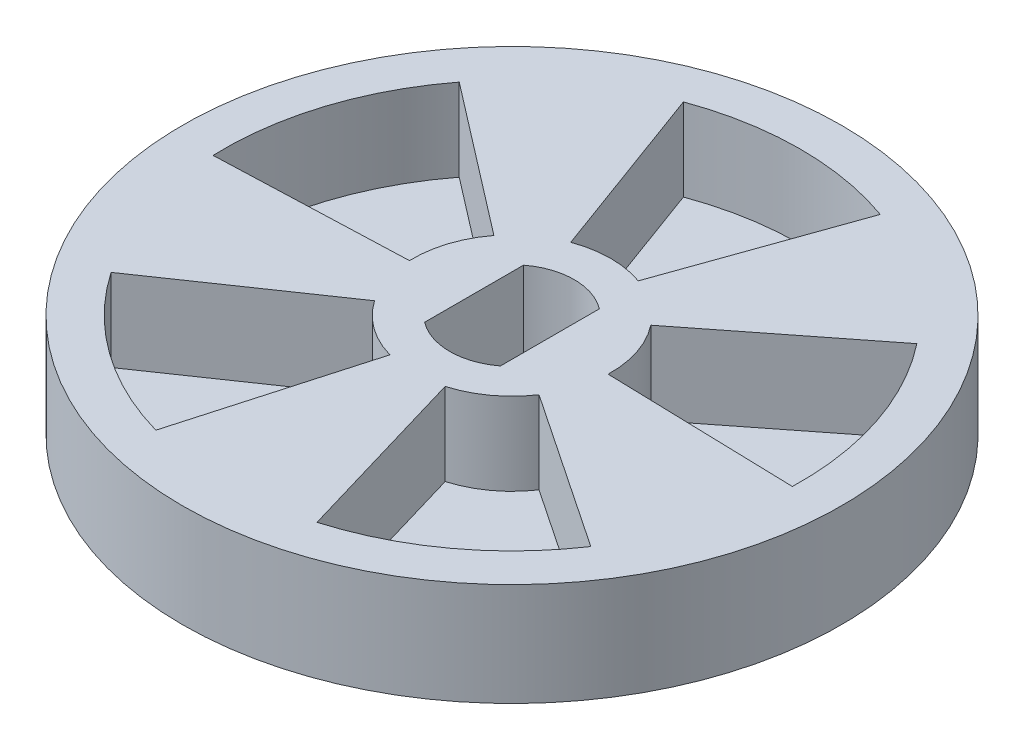
SolidWorks part; units mm, degrees
ref_plane "Front Plane" through (0, 0, 0) normal (0, 0, 1) x (1, 0, 0)
ref_plane "Top Plane" through (0, 0, 0) normal (0, 1, 0) x (1, 0, 0)
ref_plane "Right Plane" through (0, 0, 0) normal (1, 0, 0) x (0, 0, -1)
sketch "Sketch1" plane through (0, 0, 0) normal (0, 1, 0) x (1, 0, 0)
  line L0 (-2.9196, 3.81) -> (-2.9196, -3.81)
  line L1 (2.9196, 3.81) -> (2.9196, -3.81)
  circle A0 centre (0, 0) radius 4.8
  circle A1 centre (0, 0) radius 25.4
  dimension "D1" = 9.6
  dimension "D3" = 50.8
  dimension "D2" = 7.62
extrude "Boss-Extrude1" add sketch "Sketch1" along normal blind 6.35 contours A1 A0 | L0 A0 | L1 A0 region at (-3.686, 0, 0) region at (3.686, 0, 0) region at (-24.6816, 0, 0)
sketch "Sketch5" plane through (0, 0, 0) normal (0, 1, 0) x (1, 0, 0)
  circle A0 centre (0, 0) radius 25.4
extrude "Boss-Extrude2" add sketch "Sketch5" against normal blind 1.5875
sketch "Sketch6" plane through (0, 6.35, 0) normal (0, 1, 0) x (1, 0, 0)
  line L0 (-17.617, 13.5496) -> (-6.0401, 4.6456)
  line L1 (-22.2095, -0.8309) -> (-7.6147, -0.2849)
  circle A0 centre (0, 0) radius 7.62
  circle A1 centre (0, 0) radius 22.225
  dimension "D1" = 15.24
  dimension "D2" = 44.45
extrude "Cut-Extrude1" cut sketch "Sketch6" against normal up to surface (6.35 mm away) contours L0 A1 L1 A0 region at (-15.0446, 6.35, -4.8046) up to face at (0, 0, 0)
pattern_circular "CirPattern2" count 5 over 360 about axis through (0, 6.35, 0) along (0, 1, 0) of "Cut-Extrude1"
